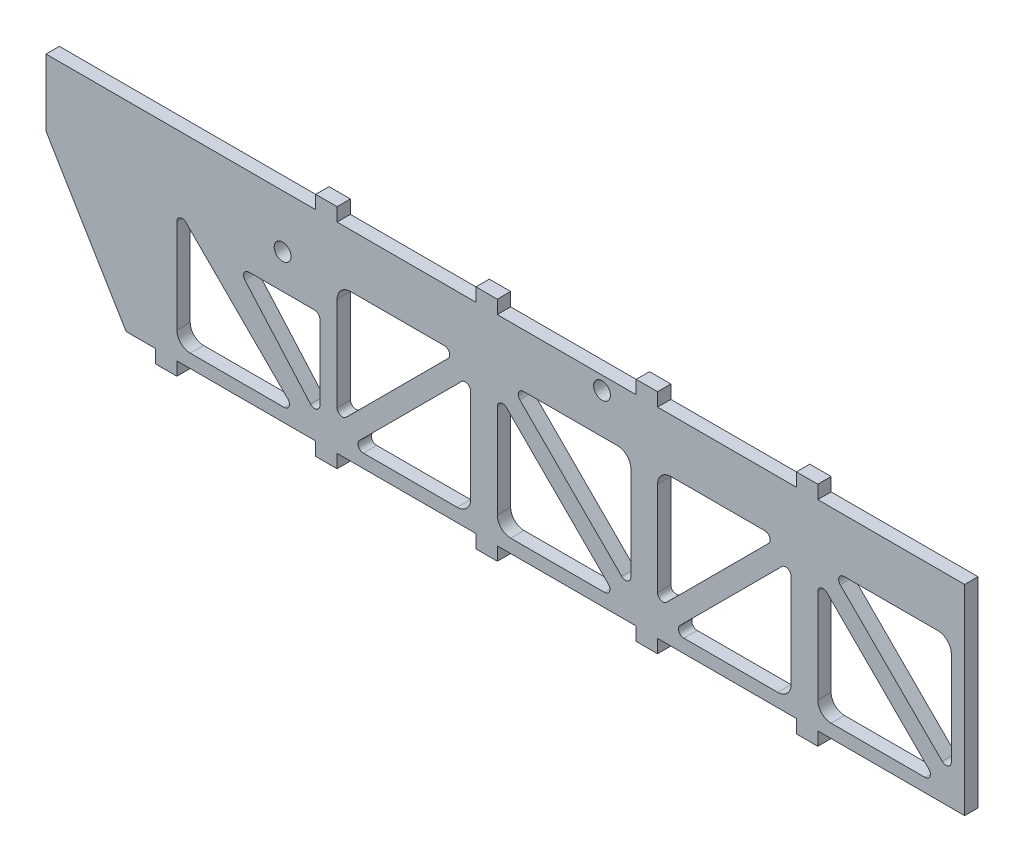
SolidWorks part; units mm, degrees
material "Pine"
ref_plane "Front Plane" through (0, 0, 0) normal (0, 0, 1) x (1, 0, 0)
ref_plane "Top Plane" through (0, 0, 0) normal (0, 1, 0) x (1, 0, 0)
ref_plane "Right Plane" through (0, 0, 0) normal (1, 0, 0) x (0, 0, -1)
sketch "Model" plane through (0, 0, 0) normal (0, 0, 1) x (1, 0, 0)
  line L0 (-306.6281, 15.625) -> (-306.6281, 51.1493)
  line L1 (-309.1681, 53.6893) -> (-340.406, 53.6893)
  line L2 (-342.3135, 49.472) -> (-311.0755, 13.9477)
  line L8 (-171.2321, 6.35) -> (-215.9, 6.35)
  line L9 (-222.25, 57.3679) -> (-222.25, 12.7)
  line L10 (-217.9139, 59.1639) -> (-169.4361, 10.6861)
  line L11 (-234.95, 57.3679) -> (-234.95, 12.7)
  line L12 (-241.3, 6.35) -> (-285.9679, 6.35)
  line L13 (-239.2861, 59.1639) -> (-287.7639, 10.6861)
  line L14 (-294.1139, 17.0361) -> (-245.6361, 65.5139)
  line L15 (-298.45, 63.5) -> (-298.45, 18.8321)
  line L16 (-247.4321, 69.85) -> (-292.1, 69.85)
  line L17 (-323.6321, 6.35) -> (-368.3, 6.35)
  line L18 (-374.65, 57.3679) -> (-374.65, 12.7)
  line L19 (-370.3139, 59.1639) -> (-321.8361, 10.6861)
  line L20 (-18.8321, 6.35) -> (-63.5, 6.35)
  line L21 (-69.85, 57.3679) -> (-69.85, 12.7)
  line L22 (-17.0361, 10.6861) -> (-65.5139, 59.1639)
  line L23 (-82.55, 57.3679) -> (-82.55, 12.7)
  line L24 (-88.9, 6.35) -> (-133.5679, 6.35)
  line L25 (-86.8861, 59.1639) -> (-135.3639, 10.6861)
  line L26 (-93.2361, 65.5139) -> (-141.7139, 17.0361)
  line L27 (-146.05, 63.5) -> (-146.05, 18.8321)
  line L28 (-95.0321, 69.85) -> (-139.7, 69.85)
  line L29 (-163.0861, 17.0361) -> (-211.5639, 65.5139)
  line L30 (-165.1, 69.85) -> (-209.7679, 69.85)
  line L31 (-158.75, 63.5) -> (-158.75, 18.8321)
  line L35 (-398.78, 0) -> (-436.88, 63.5)
  line L36 (0, 0) -> (-398.78, 0)
  line L37 (0, 0) -> (0, 95.25)
  line L38 (0, 95.25) -> (-436.88, 95.25)
  line L39 (-436.88, 63.5) -> (-436.88, 95.25)
  line L40 (-6.35, 63.5) -> (-6.35, 18.8321)
  line L41 (-59.1639, 65.5139) -> (-10.6861, 17.0361)
  line L42 (-12.7, 69.85) -> (-57.3679, 69.85)
  arc A0 (-222.25, 12.7) -> (-215.9, 6.35) centre (-215.9, 12.7) ccw
  arc A1 (-217.9139, 59.1639) -> (-222.25, 57.3679) centre (-219.71, 57.3679) ccw
  arc A2 (-171.2321, 6.35) -> (-169.4361, 10.6861) centre (-171.2321, 8.89) ccw
  arc A3 (-234.95, 57.3679) -> (-239.2861, 59.1639) centre (-237.49, 57.3679) ccw
  arc A4 (-241.3, 6.35) -> (-234.95, 12.7) centre (-241.3, 12.7) ccw
  arc A5 (-287.7639, 10.6861) -> (-285.9679, 6.35) centre (-285.9679, 8.89) ccw
  arc A6 (-245.6361, 65.5139) -> (-247.4321, 69.85) centre (-247.4321, 67.31) ccw
  arc A7 (-298.45, 18.8321) -> (-294.1139, 17.0361) centre (-295.91, 18.8321) ccw
  arc A8 (-292.1, 69.85) -> (-298.45, 63.5) centre (-292.1, 63.5) ccw
  arc A9 (-323.6321, 6.35) -> (-321.8361, 10.6861) centre (-323.6321, 8.89) ccw
  arc A10 (-374.65, 12.7) -> (-368.3, 6.35) centre (-368.3, 12.7) ccw
  arc A11 (-370.3139, 59.1639) -> (-374.65, 57.3679) centre (-372.11, 57.3679) ccw
  arc A12 (-69.85, 12.7) -> (-63.5, 6.35) centre (-63.5, 12.7) ccw
  arc A13 (-65.5139, 59.1639) -> (-69.85, 57.3679) centre (-67.31, 57.3679) ccw
  arc A14 (-18.8321, 6.35) -> (-17.0361, 10.6861) centre (-18.8321, 8.89) ccw
  arc A15 (-82.55, 57.3679) -> (-86.8861, 59.1639) centre (-85.09, 57.3679) ccw
  arc A16 (-88.9, 6.35) -> (-82.55, 12.7) centre (-88.9, 12.7) ccw
  arc A17 (-135.3639, 10.6861) -> (-133.5679, 6.35) centre (-133.5679, 8.89) ccw
  arc A18 (-93.2361, 65.5139) -> (-95.0321, 69.85) centre (-95.0321, 67.31) ccw
  arc A19 (-146.05, 18.8321) -> (-141.7139, 17.0361) centre (-143.51, 18.8321) ccw
  arc A20 (-139.7, 69.85) -> (-146.05, 63.5) centre (-139.7, 63.5) ccw
  arc A21 (-163.0861, 17.0361) -> (-158.75, 18.8321) centre (-161.29, 18.8321) ccw
  arc A22 (-209.7679, 69.85) -> (-211.5639, 65.5139) centre (-209.7679, 67.31) ccw
  arc A23 (-158.75, 63.5) -> (-165.1, 69.85) centre (-165.1, 63.5) ccw
  arc A24 (-306.6281, 15.625) -> (-311.0755, 13.9477) centre (-309.1681, 15.625) cw
  arc A25 (-340.406, 53.6893) -> (-342.3135, 49.472) centre (-340.406, 51.1493) ccw
  arc A26 (-306.6281, 51.1493) -> (-309.1681, 53.6893) centre (-309.1681, 51.1493) ccw
  arc A27 (-10.6861, 17.0361) -> (-6.35, 18.8321) centre (-8.89, 18.8321) ccw
  arc A28 (-57.3679, 69.85) -> (-59.1639, 65.5139) centre (-57.3679, 67.31) ccw
  arc A29 (-6.35, 63.5) -> (-12.7, 69.85) centre (-12.7, 63.5) ccw
  circle A30 centre (-172.466, 88.9) radius 4
  circle A31 centre (-324.358, 70.104) radius 4
  dimension "D2" = 172.466
  dimension "D4" = 8
  dimension "D5" = 151.892
  dimension "D7" = 8
  dimension "D6" = 18.796
  dimension "D8" = 2.54
  dimension "D1" = 95.25
  dimension "D3" = 6.35
extrude "Boss-Extrude1" add sketch "Model" along normal blind 6.35
sketch "Sketch1" plane through (0, 0, 6.35) normal (0, 0, 1) x (1, 0, 0)
  line L0 (-69.85, 95.25) -> (-69.85, 0) construction
  line L1 (-69.85, 57.3679) -> (-69.85, 12.7) construction
  line L2 (-398.78, 0) -> (0, 0) construction
  line L3 (-146.05, 95.25) -> (-146.05, 0) construction
  line L4 (-146.05, 63.5) -> (-146.05, 18.8321) construction
  line L5 (-222.25, 95.25) -> (-222.25, 0) construction
  line L6 (-222.25, 57.3679) -> (-222.25, 12.7) construction
  line L7 (-298.45, 95.25) -> (-298.45, 0) construction
  line L8 (-298.45, 63.5) -> (-298.45, 18.8321) construction
  line L9 (-374.65, 95.25) -> (-374.65, 0) construction
  line L10 (-374.65, 57.3679) -> (-374.65, 12.7) construction
  line L11 (0, 95.25) -> (-436.88, 95.25) construction
  line L12 (-69.85, 0) -> (-80.01, 0)
  line L13 (-69.85, 0) -> (-69.85, -6.35)
  line L14 (-69.85, -6.35) -> (-80.01, -6.35)
  line L15 (-80.01, 0) -> (-80.01, -6.35)
  line L16 (-146.05, 0) -> (-156.21, 0)
  line L17 (-146.05, 0) -> (-146.05, -6.35)
  line L18 (-146.05, -6.35) -> (-156.21, -6.35)
  line L19 (-156.21, 0) -> (-156.21, -6.35)
  line L20 (-222.25, 0) -> (-232.41, 0)
  line L21 (-222.25, 0) -> (-222.25, -6.35)
  line L22 (-222.25, -6.35) -> (-232.41, -6.35)
  line L23 (-232.41, 0) -> (-232.41, -6.35)
  line L24 (-298.45, 0) -> (-308.61, 0)
  line L25 (-298.45, 0) -> (-298.45, -6.35)
  line L26 (-298.45, -6.35) -> (-308.61, -6.35)
  line L27 (-308.61, 0) -> (-308.61, -6.35)
  line L28 (-374.65, 0) -> (-384.81, 0)
  line L29 (-374.65, 0) -> (-374.65, -6.35)
  line L30 (-374.65, -6.35) -> (-384.81, -6.35)
  line L31 (-384.81, 0) -> (-384.81, -6.35)
  line L37 (-298.45, 95.25) -> (-308.61, 95.25)
  line L38 (-298.45, 95.25) -> (-298.45, 101.6)
  line L39 (-298.45, 101.6) -> (-308.61, 101.6)
  line L40 (-308.61, 95.25) -> (-308.61, 101.6)
  line L41 (-222.25, 95.25) -> (-232.41, 95.25)
  line L42 (-222.25, 95.25) -> (-222.25, 101.6)
  line L43 (-222.25, 101.6) -> (-232.41, 101.6)
  line L44 (-232.41, 95.25) -> (-232.41, 101.6)
  line L45 (-146.05, 95.25) -> (-156.21, 95.25)
  line L46 (-146.05, 95.25) -> (-146.05, 101.6)
  line L47 (-146.05, 101.6) -> (-156.21, 101.6)
  line L48 (-156.21, 95.25) -> (-156.21, 101.6)
  line L49 (-69.85, 95.25) -> (-80.01, 95.25)
  line L50 (-69.85, 95.25) -> (-69.85, 101.6)
  line L51 (-69.85, 101.6) -> (-80.01, 101.6)
  line L52 (-80.01, 95.25) -> (-80.01, 101.6)
  dimension "D1" = 6.35
  dimension "D2" = 10.16
  dimension "D3" = 10.16
  dimension "D4" = 10.16
  dimension "D5" = 10.16
  dimension "D6" = 10.16
  dimension "D7" = 6.35
  dimension "D9" = 10.16
  dimension "D10" = 10.16
  dimension "D11" = 10.16
  dimension "D12" = 10.16
extrude "Boss-Extrude2" add sketch "Sketch1" against normal up to surface (6.35 mm away) up to face at (-168.466, 88.9, 0)
equation "\"thick\"=0.25"
equation "\"D1@Boss-Extrude1\"=\"thick\""
